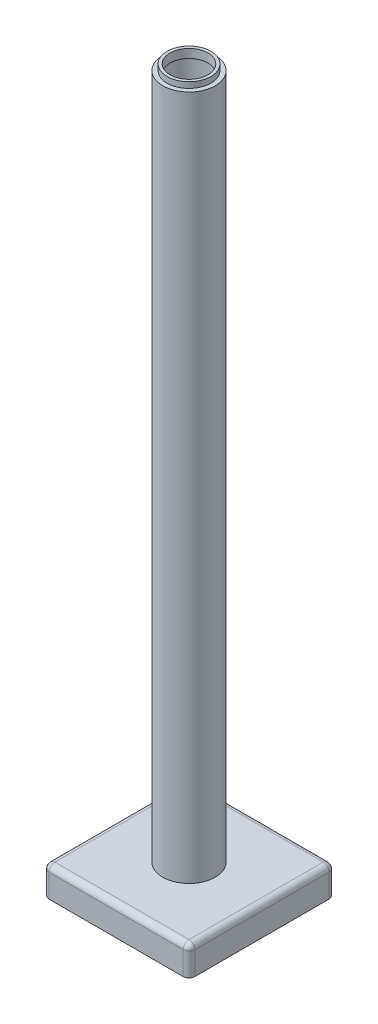
SolidWorks part; units mm, degrees
ref_plane "前视基准面" through (0, 0, 0) normal (0, 0, 1) x (1, 0, 0)
ref_plane "上视基准面" through (0, 0, 0) normal (0, 1, 0) x (1, 0, 0)
ref_plane "右视基准面" through (0, 0, 0) normal (1, 0, 0) x (0, 0, -1)
other "Configuration Table"
sketch "底座" plane through (0, 0, 0) normal (0, 1, 0) x (1, 0, 0)
  line L5 (-25, -25) -> (25, -25)
  line L6 (-25, -25) -> (-25, 25)
  line L7 (-25, 25) -> (25, 25)
  line L8 (25, -25) -> (25, 25)
  line L9 (-25, -25) -> (25, 25) construction
  line L10 (-25, 25) -> (25, -25) construction
  circle A1 centre (0, 0) radius 7.5
  point P0 (0, 0)
  dimension "D3" = 15
  dimension "D1" = 50
  dimension "D2" = 50
extrude "凸台-拉伸1" add sketch "底座" along normal blind 10
fillet "圆角2" radius 2 8 edges at (0, 10, 25) (-25, 10, 0) (0, 10, -25) (25, 10, 0) (-25, 5, -25) (25, 5, -25) (25, 5, 25) (-25, 5, 25)
sketch "圆柱" plane through (0, 10, 0) normal (0, 1, 0) x (1, 0, 0)
  circle A1 centre (0, 0) radius 9
extrude "凸台-拉伸2" add sketch "圆柱" along normal blind 235 separate body
shell "抽壳6" thickness 1.5 removed face at (0, 245, 9) removed face at (0, 10, 9)
ref_plane "基准面3" through (0, 244, 0) normal (0, 1, 0) x (1, 0, 0)
sketch "草图6" plane through (0, 244, 0) normal (0, 1, 0) x (1, 0, 0)
  circle A0 centre (0, 0) radius 7.5 construction
  circle A1 centre (0, 0) radius 7.5
extrude "凸台-拉伸5" add sketch "草图6" along normal blind 3
shell "抽壳13" thickness 1 removed face at (0, 244, 7.5) removed face at (0, 247, 7.5)
ref_plane "基准面4" through (0, 0, 0) normal (0, 0, -1) x (-1, 0, 0)
sketch "草图7" plane through (0, 0, 0) normal (0, 0, -1) x (-1, 0, 0)
  line L0 (0, 0) -> (7.5, 0) construction
  line L1 (55, 0) -> (-55, 0) construction
  line L2 (7.5, 0) -> (9, 0) construction
  line L3 (9, 10.0683) -> (9, 0) construction
  line L4 (7.5, 0) -> (7.5, 50000) construction
  line L5 (6.5, 247.0194) -> (6.5, 244.0194) construction
  dimension "D1" = 7.5
  dimension "D2" = 1.5
  dimension "D3" = 3
  dimension "D4" = 1
